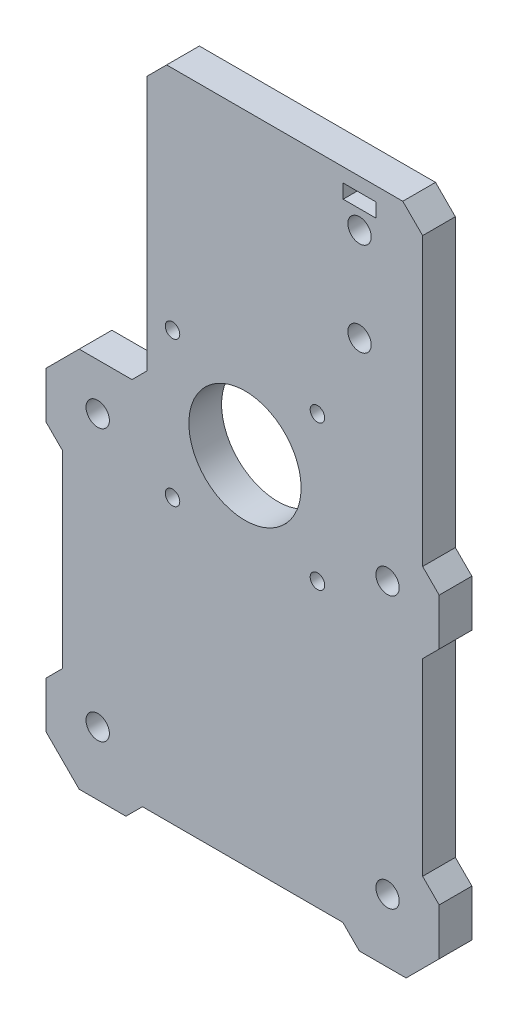
SolidWorks part; units mm, degrees
ref_plane "Alzado" through (0, 0, 0) normal (0, 0, 1) x (1, 0, 0)
ref_plane "Planta" through (0, 0, 0) normal (0, 1, 0) x (1, 0, 0)
ref_plane "Vista lateral" through (0, 0, 0) normal (1, 0, 0) x (0, 0, -1)
sketch "Croquis1" plane through (0, 0, 0) normal (0, 0, 1) x (1, 0, 0)
  line L0 (0, 0) -> (0, 36.5) construction
  line L5 (31, 29) -> (-31, 29)
  line L10 (31, 29) -> (31, -29)
  line L11 (31, -29) -> (-31, -29)
  line L12 (-31, 29) -> (-31, -29)
  line L13 (31, 29) -> (-31, -29) construction
  line L14 (31, -29) -> (-31, 29) construction
  line L15 (-38.5, 39) -> (-20.5, 39)
  line L16 (-38.5, 39) -> (-38.5, -39)
  line L17 (-38.5, -39) -> (38.5, -39)
  line L18 (38.5, 39) -> (38.5, -39)
  line L19 (-38.5, 39) -> (38.5, -39) construction
  line L20 (-38.5, -39) -> (38.5, 39) construction
  line L21 (38.5, 39) -> (38.5, 96.7574)
  line L26 (34.2574, 101) -> (-16.2574, 101)
  line L27 (-20.5, 96.7574) -> (-20.5, 39)
  line L28 (34.2574, 101) -> (38.5, 96.7574)
  line L29 (-16.2574, 101) -> (-20.5, 96.7574)
  circle A0 centre (-31, 29) radius 2.5
  circle A1 centre (31, 29) radius 2.5
  circle A2 centre (31, -29) radius 2.5
  circle A3 centre (-31, -29) radius 2.5
  point P0 (0, 0)
  point P5 (0, 0)
  dimension "D5" = 36.5
  dimension "D6" = 62
  dimension "D1" = 62
  dimension "D2" = 58
  dimension "D3" = 78
  dimension "D4" = 77
  dimension "D7" = 59
  dimension "D8" = 135
  dimension "D9" = 6
  dimension "D10" = 45
  dimension "D11" = 6
extrude "Saliente-Extruir1" add sketch "Croquis1" along normal blind 7 contours L26 L29 L27 L15 L16 L17 L18 L21 L28 A3 L12 A0 L5 A1 L10 A2 L11 | A3 L11 A2 L10 A1 L5 A0 L12 region at (0, 0, 0) region at (5.4681, 42.4409, 0)
sketch "Croquis9" plane through (0, 0, 7) normal (0, 0, 1) x (1, 0, 0)
  line L0 (21.4289, -39) -> (24.9645, -42.5355)
  line L1 (-38.5, -39) -> (38.5, -39) construction
  line L2 (24.9645, -42.5355) -> (34.9645, -42.5355)
  line L3 (34.9645, -42.5355) -> (42.0355, -35.4645)
  line L4 (42.0355, -35.4645) -> (42.0355, -25.4645)
  line L5 (42.0355, -25.4645) -> (38.5, -21.9289)
  line L6 (38.5, 96.7574) -> (38.5, -39) construction
  line L7 (0, -55) -> (0, 55) construction
  line L8 (-42.0355, -25.4645) -> (-38.5, -21.9289)
  line L9 (-42.0355, -35.4645) -> (-42.0355, -25.4645)
  line L10 (-34.9645, -42.5355) -> (-42.0355, -35.4645)
  line L11 (-24.9645, -42.5355) -> (-34.9645, -42.5355)
  line L12 (-21.4289, -39) -> (-24.9645, -42.5355)
  line L13 (-38.5, -21.9289) -> (-38.5, -30.4645)
  line L14 (-29.9645, -39) -> (-21.4289, -39)
  line L15 (-29.9645, -39) -> (-38.5, -30.4645)
  line L16 (38.5, -21.9289) -> (38.5, -30.4645)
  line L17 (29.9645, -39) -> (21.4289, -39)
  line L18 (29.9645, -39) -> (38.5, -30.4645)
  line L19 (-38.5, 39) -> (-20.5, 39) construction
  line L21 (-23.668, 39) -> (-20.1325, 42.5355)
  line L22 (-34.9645, 39) -> (-42.0355, 31.9289)
  line L23 (-42.0355, 31.9289) -> (-42.0355, 21.9289)
  line L24 (-42.0355, 21.9289) -> (-38.5, 18.3934)
  line L25 (-38.5, 39) -> (-38.5, -39) construction
  line L26 (42.0355, 21.9289) -> (38.5, 18.3934)
  line L27 (42.0355, 31.9289) -> (42.0355, 21.9289)
  line L28 (34.9645, 39) -> (42.0355, 31.9289)
  line L29 (-34.9645, 39) -> (-38.5, 18.3934)
  line L30 (38.5, 18.3934) -> (34.9645, 39)
  line M29 (-20.5, 96.7574) -> (-20.5, 39)
  line M30 (-20.5, 39) -> (-38.5, 39)
  line M31 (-38.5, 39) -> (-38.5, -39)
  line M32 (-38.5, -39) -> (38.5, -39)
  line M33 (38.5, -39) -> (38.5, 96.7574)
  dimension "D1" = 45
  dimension "D2" = 45
  dimension "D3" = 10
  dimension "D4" = 10
  dimension "D5" = 10
  dimension "D6" = 5
  dimension "D7" = 5
  dimension "D8" = 45
  dimension "D10" = 10
  dimension "D12" = 10
  dimension "D13" = 135
  dimension "D14" = 5
extrude "Saliente-Extruir2" add sketch "Croquis9" against normal through all contours L29 L22 M31 | L23 L24 L22 M31 | L30 L28 M33 | L28 L26 L27 M33 | L4 L5 L3 M33 | L2 L3 L0 M32 | L18 M32 M33 | L10 L8 L9 M31 | L15 M32 M31 | L12 L10 L11 M32 | L21 M30 M29 region at (29.9645, -40.6139, 7) region at (37.3215, 30.9526, 7) region at (40.1139, 26.9289, 7) region at (-21.556, 40.056, 7) region at (-40.1139, 26.9289, 7) region at (-37.3215, 30.9526, 7) region at (-29.9645, -40.6139, 7) region at (35.6548, -36.1548, 7) region at (40.1139, -30.4645, 7) region at (-35.6548, -36.1548, 7) region at (-40.1139, -30.4645, 7)
sketch "Croquis10" plane through (0, 0, 7) normal (0, 0, 1) x (1, 0, 0)
  line L0 (-38.5, 35.4645) -> (-34.9645, 39)
  line L1 (-38.5, 39) -> (-23.668, 39) construction
  line L2 (-34.9645, 39) -> (-38.5, 39)
  line L3 (-38.5, 39) -> (-38.5, 35.4645)
  line L4 (38.5, 91) -> (25, 91) construction
  line L5 (38.5, 96.7574) -> (38.5, 35.4645) construction
  line L6 (34.2574, 101) -> (-16.2574, 101) construction
  line L7 (-38.5, 18.3934) -> (-38.5, -21.9289) construction
  line L8 (-21.4289, -39) -> (21.4289, -39) construction
  line L14 (-15, 52.5) -> (16, 21.5) construction
  line L15 (-15, 21.5) -> (16, 52.5) construction
  line L16 (16, 21.5) -> (-15, 21.5)
  line L17 (16, 21.5) -> (16, 52.5)
  line L18 (16, 52.5) -> (-15, 52.5)
  line L19 (-15, 21.5) -> (-15, 52.5)
  line L20 (16, 21.5) -> (-15, 52.5) construction
  line L21 (16, 52.5) -> (-15, 21.5) construction
  circle A0 centre (25, 91) radius 2.5
  circle A1 centre (-15, 52.5) radius 1.55
  circle A2 centre (25, 71) radius 2.5
  circle A3 centre (0.5, 37) radius 12
  circle A4 centre (16, 52.5) radius 1.55
  circle A5 centre (16, 21.5) radius 1.55
  circle A6 centre (-15, 21.5) radius 1.55
  point P36 (0.5, 37)
  line M22 (-23.668, 39) -> (-38.5, 39)
  line M23 (-38.5, 39) -> (-38.5, 35.4645)
  dimension "D1" = 13.5
  dimension "D2" = 5
  dimension "D3" = 10
  dimension "D5" = 24
  dimension "D8" = 3.1
  dimension "D6" = 39
  dimension "D7" = 76
  dimension "D9" = 4
  dimension "D10" = 20
  dimension "D4" = 2
extrude "BarrenosNEMA" cut sketch "Croquis10" against normal through all contours L0 M23 M22 | A2 | A0 | A3 | A1 | A4 | A5 | A6 region at (-37.3215, 37.8215, 7) region at (25, 91, 7) region at (25, 71, 7) region at (0.5, 37, 7)
sketch "Croquis11" plane through (0, 0, 7) normal (0, 0, 1) x (1, 0, 0)
  line L0 (25, 91) -> (25, 96.5)
  line L2 (21.5, 98) -> (28.5, 98)
  line L3 (21.5, 98) -> (21.5, 95)
  line L4 (21.5, 95) -> (28.5, 95)
  line L5 (28.5, 98) -> (28.5, 95)
  line L6 (21.5, 98) -> (28.5, 95) construction
  line L7 (21.5, 95) -> (28.5, 98) construction
  dimension "D1" = 7
  dimension "D2" = 3
  dimension "D3" = 5.5
extrude "Cortar-Extruir2" cut sketch "Croquis11" against normal blind 10 contours L5 L2 L3 L4 region at (25, 97.9238, 7)
